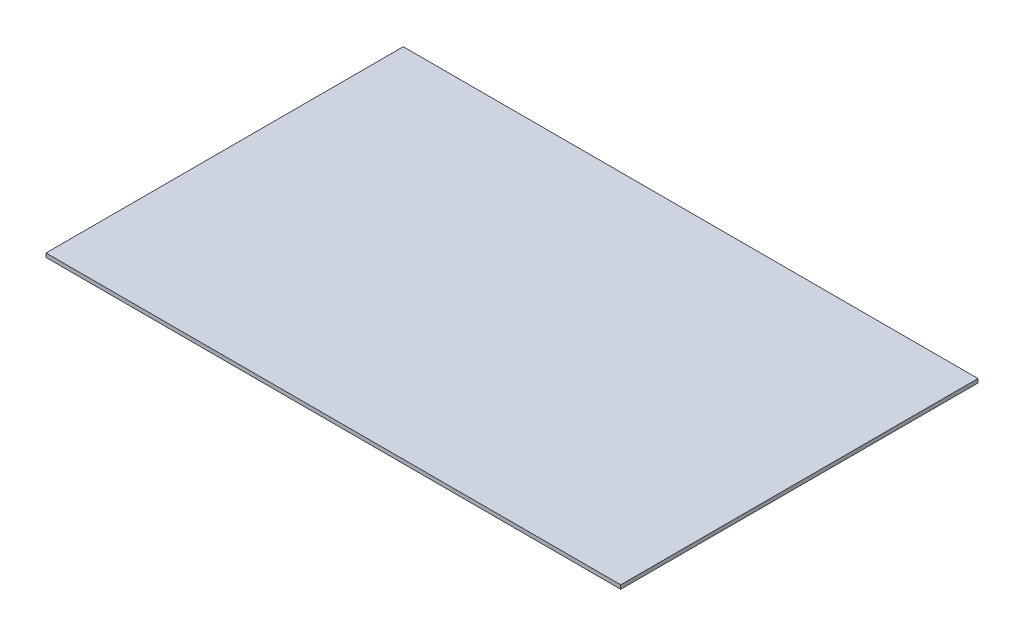
SolidWorks part; units mm, degrees
material "Бальса"
ref_plane "Спереди" through (0, 0, 0) normal (0, 0, 1) x (1, 0, 0)
ref_plane "Сверху" through (0, 0, 0) normal (0, 1, 0) x (1, 0, 0)
ref_plane "Справа" through (0, 0, 0) normal (1, 0, 0) x (0, 0, -1)
sketch "Эскиз1" plane through (0, 0, 0) normal (0, 1, 0) x (1, 0, 0)
  line L1 (0, 0) -> (1480, 0)
  line L2 (0, 0) -> (0, 920)
  line L3 (0, 920) -> (1480, 920)
  line L4 (1480, 0) -> (1480, 920)
  dimension "D1" = 920
  dimension "D2" = 1480
extrude "Бобышка-Вытянуть1" add sketch "Эскиз1" along normal blind 10
